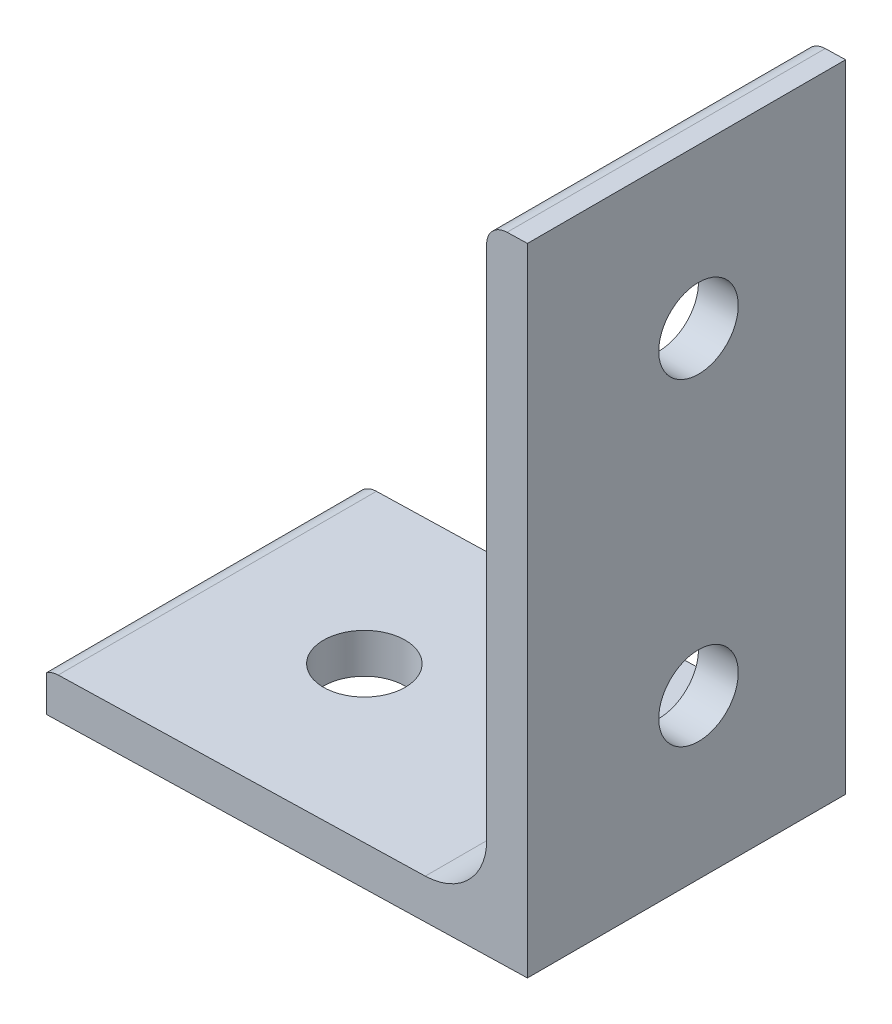
SolidWorks part; units mm, degrees
ref_plane "Front Plane" through (0, 0, 0) normal (0, 0, 1) x (1, 0, 0)
ref_plane "Top Plane" through (0, 0, 0) normal (0, 1, 0) x (1, 0, 0)
ref_plane "Right Plane" through (0, 0, 0) normal (1, 0, 0) x (0, 0, -1)
sketch "Sketch0" plane through (0, 0, 0) normal (0, 0, 1) x (1, 0, 0)
  line L0 (-19.05, -25.4) -> (19.05, -25.4)
  line L1 (19.05, -25.4) -> (19.05, 25.4)
  line L2 (19.05, 0) -> (0, 0) construction
  line L3 (0, 0) -> (0, -25.4) construction
  line L4 (15.875, -17.4498) -> (15.875, 25.4) construction
  line L5 (11.0998, -22.225) -> (-19.05, -22.225) construction
  arc A0 (15.875, -17.4498) -> (11.0998, -22.225) centre (11.0998, -17.4498) cw
  point P3 (14.4764, -20.8264)
  dimension "Inside Corner Radius" = 4.7752
  dimension "Outside Height" = 50.8
  dimension "Inside Height" = 47.625
  dimension "Inside Width" = 34.925
  dimension "Wall Thickness" = 3.175
  dimension "D1" = 3.175
  dimension "Outside Width" = 38.1
sketch "Sketch1" plane through (0, 0, 0) normal (1, 0, 0) x (0, 0, -1)
  line L0 (15.875, 0) -> (-15.875, 0)
  point P4 (0, 0)
  dimension "Length" = 31.75
sketch "Sketch2" plane through (0, 0, 0) normal (0, 0, 1) x (1, 0, 0)
  line L0 (-19.05, -25.4) -> (19.05, -25.4)
  line L1 (19.05, -25.4) -> (19.05, 25.4)
  line L2 (19.05, 25.4) -> (15.875, 25.4) construction
  line L3 (15.875, 23.8125) -> (15.875, -17.4498)
  line L4 (11.0998, -22.225) -> (-17.4625, -22.225)
  line L5 (-19.05, -25.4) -> (-19.05, -22.225) construction
  line L6 (17.4625, 25.4) -> (19.05, 25.4)
  line L7 (-19.05, -23.8125) -> (-19.05, -25.4)
  line L8 (19.05, 0) -> (0, 0) construction
  line L9 (0, 0) -> (0, -25.4) construction
  arc A0 (15.875, 23.8125) -> (17.4625, 25.4) centre (17.4625, 23.8125) cw
  arc A1 (-19.05, -23.8125) -> (-17.4625, -22.225) centre (-17.4625, -23.8125) cw
  arc A2 (15.875, -17.4498) -> (11.0998, -22.225) centre (11.0998, -17.4498) cw
  dimension "Inside Radius" = 4.7752
  dimension "Height" = 50.8
  dimension "Width" = 38.1
  dimension "Thickness" = 3.175
extrude "Boss-Extrude1" add sketch "Sketch2" along normal mid plane 31.75
sketch "Break Locations" plane through (0, 0, 0) normal (1, 0, 0) x (0, 0, -1)
  line L0 (35.941, 0) -> (-35.941, 0)
  line L1 (-15.875, -25.4) -> (-15.875, 25.4) construction
  line L2 (15.875, -25.4) -> (15.875, 25.4) construction
  point P0 (27.305, 0)
  point P1 (-27.305, 0)
  point P10 (0, 0)
  point P11 (-35.941, 0)
  point P13 (35.941, 0)
  dimension "D1" = 43.18
  dimension "D2" = 43.18
  dimension "D3" = 51.816
sketch "Sketch3" plane through (0, -25.4, 0) normal (0, -1, 0) x (1, 0, 0)
  line L0 (-19.05, -13.9268) -> (19.05, -14.9245)
  line L1 (19.05, 15.875) -> (19.05, -15.875) construction
  line L2 (19.05, -14.9245) -> (15.875, -14.8414) construction
  line L3 (-19.05, -13.9268) -> (-18.3851, 11.4645)
  line L4 (-18.3851, 11.4645) -> (19.05, 10.4842)
  line L5 (19.05, 10.4842) -> (19.05, -14.9245)
sketch "Sketch4" plane through (19.05, 0, 0) normal (1, 0, 0) x (0, 0, -1)
  line L0 (15.875, -25.4) -> (3.175, -25.4) construction
  line L1 (-15.875, -25.4) -> (15.875, -25.4) construction
  line L2 (3.175, -25.4) -> (3.175, -12.7) construction
  line L3 (3.175, -12.7) -> (3.175, 12.7) construction
  circle A0 centre (3.175, 12.7) radius 3.175
  circle A1 centre (3.175, -12.7) radius 3.175
  dimension "D1" = 12.7
  dimension "D2" = 12.7
  dimension "D3" = 25.4
extrude "Cut-Extrude1" cut sketch "Sketch4" against normal through all
extrude "Cut-Extrude2" cut sketch "Sketch3" against normal through all flip side to cut
hole_wizard "1/4 Clearance Hole1" positions "Sketch7" profile "Sketch8" hole size "1/4" standard "ANSI Inch" end condition through all
sketch "Sketch7" plane through (0, -25.4, 0) normal (0, -1, 0) x (-1, 0, 0)
  point P0 (6.0219, 1.5636)
sketch "Sketch8" plane through (-6.0219, -25.4, -1.5636) normal (1, 0, 0) x (0, 0, -1)
  line L0 (0, 0) -> (0, 50.8)
  line L1 (0, 50.8) -> (3.2639, 50.8)
  line L2 (3.2639, 50.8) -> (3.2639, 0)
  line L5 (3.2639, 0) -> (0, 0)
  line L11 (0, -6.35) -> (0, 107.95) construction
  dimension "Thru Hole Dia." = 6.5278
  dimension "Thru Hole Depth" = 50.8
equation "\"D1@Break Locations\" = .85 * \"Height@Sketch2\""
equation "\"D2@Break Locations\"=\"D1@Break Locations\""
equation "\"Thickness@Sketch2\"=\"wall thickness@sketch0\""
equation "\"Height@Sketch2\"=\"outside height@sketch0\""
equation "\"Width@Sketch2\"=\"outside width@sketch0\""
equation "\"Inside Radius@Sketch2\"=\"inside corner radius@sketch0\""
equation "\"Length@Boss-Extrude1\"=\"length@sketch1\""
equation "\"D3@Break Locations\"=\"D2@Break Locations\"*1.2"
equation "\"D1@Sketch0\"=\"Wall Thickness@Sketch0\""
